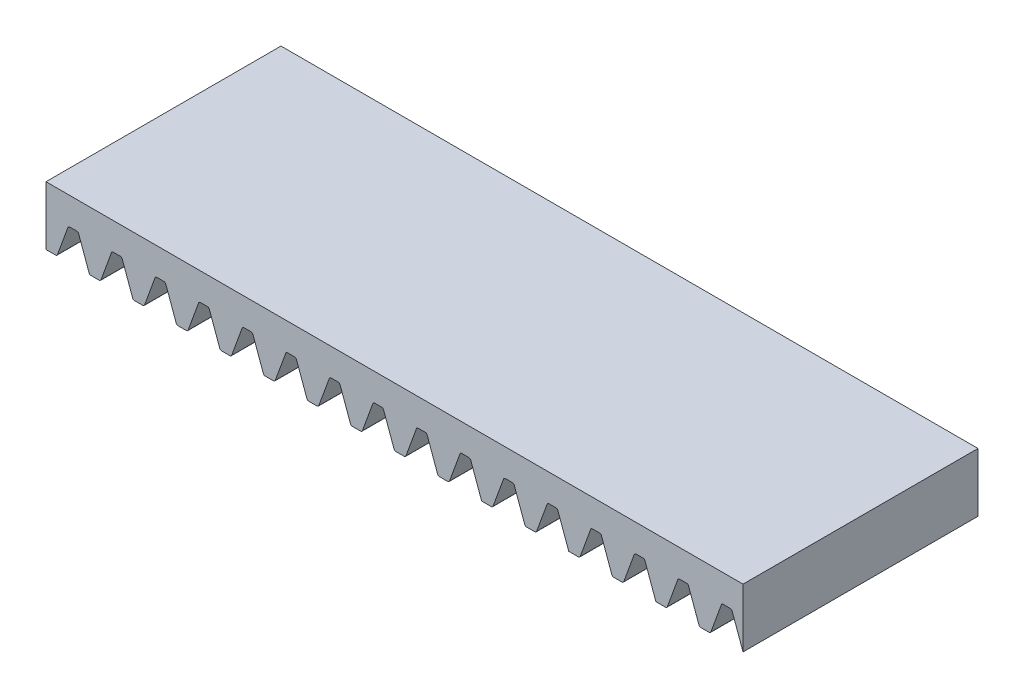
SolidWorks part; units mm, degrees
ref_plane "Front Plane" through (0, 0, 0) normal (0, 0, 1) x (1, 0, 0)
ref_plane "Top Plane" through (0, 0, 0) normal (0, 1, 0) x (1, 0, 0)
ref_plane "Right Plane" through (0, 0, 0) normal (1, 0, 0) x (0, 0, -1)
sketch "Sketch1" plane through (0, 0, 0) normal (0, 0, 1) x (1, 0, 0)
  line L0 (0, 0) -> (2.8, 0)
  line L1 (2.8, 0) -> (5.7118, 8)
  line L2 (5.7118, 8) -> (8.2118, 8)
  line L3 (8.2118, 8) -> (11.1235, 0)
  line L4 (11.1235, 0) -> (13.9235, 0)
  line L5 (13.9235, 0) -> (16.8353, 8)
  line L6 (16.8353, 8) -> (19.3353, 8)
  line L7 (19.3353, 8) -> (22.247, 0)
  line L8 (0, 0) -> (0, 15)
  line L9 (0, 15) -> (22.247, 15)
  line L10 (22.247, 15) -> (22.247, 0)
  dimension "D1" = 2.8
  dimension "D2" = 2.5
  dimension "D3" = 8
  dimension "D4" = 20
  dimension "D5" = 15
  dimension "D7" = 11.1235
extrude "Boss-Extrude1" add sketch "Sketch1" along normal blind 60
fillet "Fillet1" radius 0.5 7 edges at (19.3353, 8, 30) (16.8353, 8, 30) (13.9235, 0, 30) (2.8, 0, 30) (11.1235, 0, 30) (8.2118, 8, 30) (5.7118, 8, 30)
pattern_linear "LPattern1" count 8 spacing 22.247 along (1, 0, 0) of bodies 101
combine bodies "Combine1" operation type add bodies to combine 101 102 103 104 105 107 108 109
fillet "Fillet2" radius 0.5 4 edges at (88.9882, 0, 30) (66.7411, 0, 30) (44.4941, 0, 30) (22.247, 0, 30)
